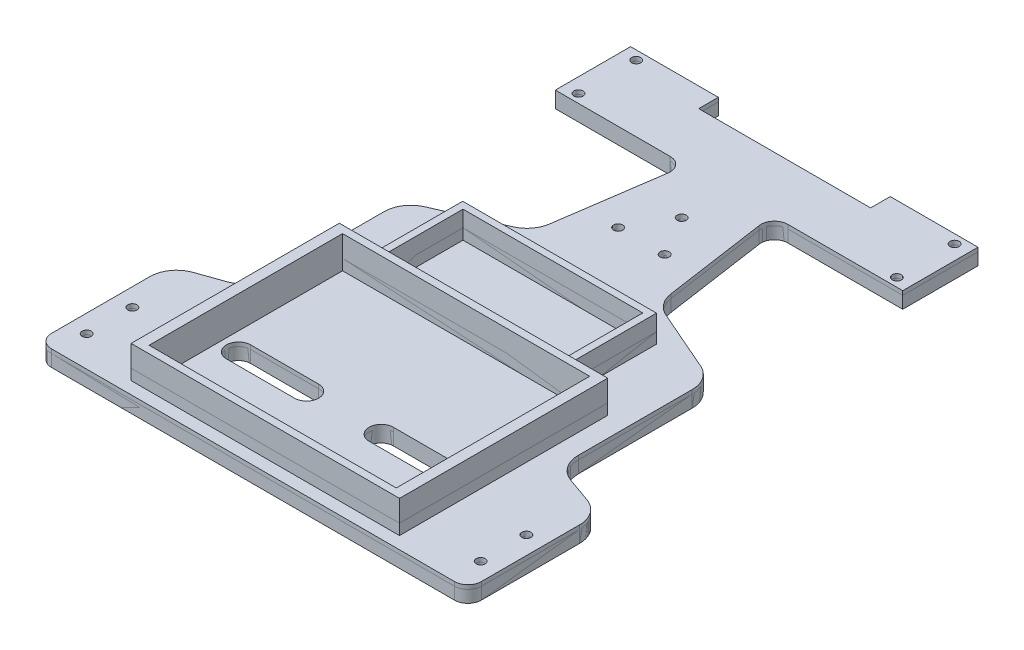
SolidWorks part; units mm, degrees
ref_plane "Front Plane" through (0, 0, 0) normal (0, 0, 1) x (1, 0, 0)
ref_plane "Top Plane" through (0, 0, 0) normal (0, 1, 0) x (1, 0, 0)
ref_plane "Right Plane" through (0, 0, 0) normal (1, 0, 0) x (0, 0, -1)
sketch "Sketch1" plane through (0, 0, 0) normal (0, 1, 0) x (1, 0, 0)
  line L1 (0, 123.1189) -> (0, -114.6431) construction
  line L5 (-80, -40.5061) -> (-80, -77.076)
  line L6 (-75, -82.076) -> (75, -82.076)
  line L28 (-51.3397, 33.1936) -> (-28.4659, 43.1635)
  line L36 (51.3397, 33.1936) -> (28.4487, 43.171)
  line L38 (-16.9584, 89.3848) -> (-22.566, 50.8891)
  line L39 (80, -40.5061) -> (80, -77.076)
  line L41 (-57.3441, 24.0265) -> (-57.3441, -18.3632)
  line L43 (57.3441, 24.0265) -> (57.3441, -18.3632)
  line L44 (-73.325, -31.075) -> (-64.0191, -27.7942)
  line L45 (64.0191, -27.7942) -> (73.325, -31.075)
  line L50 (-64.6552, 123.1189) -> (-64.6552, 95.1056)
  line L52 (64.6552, 123.1189) -> (64.6552, 95.1056)
  line L54 (16.9584, 89.3848) -> (22.553, 50.8682)
  line L55 (-64.6552, 95.1056) -> (-21.9062, 95.1056)
  line L56 (21.9062, 95.1056) -> (64.6552, 95.1056)
  line L61 (-32, 115.8044) -> (32, 115.8044)
  line L62 (32, 115.8044) -> (32, 123.1189)
  line L63 (-32, 115.8044) -> (-32, 123.1189)
  line L64 (-32, 123.1189) -> (-64.6552, 123.1189)
  line L65 (32, 123.1189) -> (64.6552, 123.1189)
  line L69 (13.8917, -48.2392) -> (39.2357, -48.2392) construction
  line L70 (13.8917, -43.7228) -> (39.2357, -43.7228)
  line L71 (13.8917, -52.7555) -> (39.2357, -52.7555)
  line L75 (-13.8917, -48.2392) -> (-39.2357, -48.2392) construction
  line L76 (-13.8917, -43.7228) -> (-39.2357, -43.7228)
  line L77 (-13.8917, -52.7555) -> (-39.2357, -52.7555)
  arc A1 (80, -77.076) -> (75, -82.076) centre (75, -77.076) cw
  arc A2 (-80, -77.076) -> (-75, -82.076) centre (-75, -77.076) ccw
  arc A5 (-28.4659, 43.1635) -> (-22.566, 50.8891) centre (-32.4616, 52.3305) ccw
  arc A6 (22.553, 50.8682) -> (28.4487, 43.171) centre (32.4444, 52.338) ccw
  arc A14 (-80, -40.5061) -> (-73.325, -31.075) centre (-70, -40.5061) cw
  arc A15 (73.325, -31.075) -> (80, -40.5061) centre (70, -40.5061) cw
  arc A16 (57.3441, -18.3632) -> (64.0191, -27.7942) centre (67.3441, -18.3632) ccw
  arc A17 (51.3397, 33.1936) -> (57.3441, 24.0265) centre (47.3441, 24.0265) cw
  arc A18 (-51.3397, 33.1936) -> (-57.3441, 24.0265) centre (-47.3441, 24.0265) ccw
  arc A19 (-57.3441, -18.3632) -> (-64.0191, -27.7942) centre (-67.3441, -18.3632) cw
  circle A20 centre (-59.25, 119.8044) radius 1.7
  circle A21 centre (-59.25, 98.3044) radius 1.7
  circle A22 centre (59.25, 98.3044) radius 1.7
  circle A23 centre (59.25, 119.8044) radius 1.7
  arc A24 (-16.9584, 89.3848) -> (-21.9062, 95.1056) centre (-21.9062, 90.1056) ccw
  arc A25 (16.9584, 89.3848) -> (21.9062, 95.1056) centre (21.9062, 90.1056) cw
  circle A26 centre (-73.325, -53.6654) radius 1.7
  circle A27 centre (-73.325, -70.6654) radius 1.7
  circle A28 centre (73.325, -70.6654) radius 1.7
  circle A29 centre (73.325, -53.6654) radius 1.7
  arc A32 (13.8917, -43.7228) -> (13.8917, -52.7555) centre (13.8917, -48.2392) ccw
  arc A33 (39.2357, -52.7555) -> (39.2357, -43.7228) centre (39.2357, -48.2392) ccw
  arc A36 (-13.8917, -43.7228) -> (-13.8917, -52.7555) centre (-13.8917, -48.2392) cw
  arc A37 (-39.2357, -52.7555) -> (-39.2357, -43.7228) centre (-39.2357, -48.2392) cw
  circle A39 centre (0, 77.4812) radius 1.7
  circle A40 centre (-8.6603, 62.4812) radius 1.7
  circle A41 centre (8.6603, 62.4812) radius 1.7
  point P7 (0, 98.3044)
  point P14 (0, -82.076)
  point P17 (0, -82.076)
  point P24 (-23.3677, 45.3856)
  point P29 (80, -45.2283)
  point P32 (80, -82.076)
  point P35 (-80, -82.076)
  point P38 (-80, -45.2283)
  point P39 (23.3677, 45.3856)
  point P42 (50, 34.4201)
  point P44 (-80, -33.4284)
  point P47 (80, -33.4284)
  point P51 (-50, 34.4201)
  point P52 (57.3441, -25.4409)
  point P55 (57.3441, 30.5765)
  point P58 (-57.3441, 30.5765)
  point P61 (-57.3441, -25.4409)
  point P66 (0, 95.1492)
  point P67 (0, 119.8044)
  point P69 (0, 125.9925)
  point P73 (0, 115.8044)
  point P76 (-16.1251, 95.1056)
  point P79 (16.1251, 95.1056)
  point P95 (26.5637, -48.2392)
  point P101 (0, 67.4812)
  point P109 (-26.5637, -48.2392)
  dimension "D7" = 10
  dimension "D8" = 64
  dimension "D10" = 118.5
  dimension "D11" = 7.3144
  dimension "D4" = 5
  dimension "D9" = 21.5
  dimension "D12" = 28.0133
  dimension "D13" = 32.6552
  dimension "D1" = 160
  dimension "D2" = 59.25
  dimension "D3" = 0
  dimension "D5" = 36.8477
  dimension "D6" = 116.4961
extrude "Boss-Extrude2" add sketch "Sketch1" along normal blind 6
sketch "Sketch2" plane through (0, 6, 0) normal (0, 1, 0) x (1, 0, 0)
  line L1 (46, -2.7522) -> (-46, -2.7522)
  line L2 (46, -2.7522) -> (46, -74.7522)
  line L3 (46, -74.7522) -> (-46, -74.7522)
  line L4 (-46, -2.7522) -> (-46, -74.7522)
  line L5 (46, -2.7522) -> (-46, -74.7522) construction
  line L6 (46, -74.7522) -> (-46, -2.7522) construction
  line L7 (-49.9483, -77.5045) -> (49.9483, -77.5045)
  line L8 (-49.9483, -77.5045) -> (-49.9483, 0)
  line L9 (-49.9483, 0) -> (49.9483, 0)
  line L10 (49.9483, -77.5045) -> (49.9483, 0)
  line L11 (-49.9483, -77.5045) -> (49.9483, 0) construction
  line L12 (-49.9483, 0) -> (49.9483, -77.5045) construction
  point P0 (0, -38.7522)
  point P5 (0, -38.7522)
  dimension "D1" = 92
  dimension "D2" = 72
  dimension "D3" = 3.9483
sketch "Sketch4" plane through (0, 6, 0) normal (0, 1, 0) x (1, 0, 0)
extrude "Boss-Extrude3" add sketch "Sketch2" along normal blind 12
sketch "Sketch8" plane through (0, 6, 0) normal (0, 1, 0) x (1, 0, 0)
  line L1 (-36.0682, 0.0375) -> (36.0682, 0.0375)
  line L2 (-36.0682, 0.0375) -> (-36.0682, 32.0375)
  line L3 (-36.0682, 32.0375) -> (36.0682, 32.0375)
  line L4 (36.0682, 0.0375) -> (36.0682, 32.0375)
  line L5 (-36.0682, 0.0375) -> (36.0682, 32.0375) construction
  line L6 (-36.0682, 32.0375) -> (36.0682, 0.0375) construction
  line L9 (33.4608, 29.5424) -> (-33.4608, 29.5424)
  line L10 (33.4608, 29.5424) -> (33.4608, 0.0375)
  line L11 (33.4608, 0.0375) -> (-33.4608, 0.0375)
  line L12 (-33.4608, 29.5424) -> (-33.4608, 0.0375)
  point P0 (0, 16.0375)
  point P10 (0, 29.5424)
  dimension "D1" = 72.1363
  dimension "D2" = 32
  dimension "D3" = 66.9216
extrude "Boss-Extrude7" add sketch "Sketch8" along normal blind 10 contours L12 L9 L10 L1 L4 L3 L2 region at (-35.279, 6, -16.0375)
extrude "Boss-Extrude9" add sketch "Sketch2<3>" along normal blind 4 and the other way blind 2 separate body
sketch "Sketch2<3>" plane through (0, 6, 0) normal (0, 1, 0) x (1, 0, 0) same geometry as "Sketch2"
extrude "Boss-Extrude10" add sketch "Sketch1<3>" along normal blind 0.001 and the other way blind 0.01
sketch "Sketch1<3>" plane through (0, 0, 0) normal (0, 1, 0) x (1, 0, 0) same geometry as "Sketch1"
extrude "Boss-Extrude11" add sketch "Sketch8<9>" along normal blind 4 and the other way blind 2 contours L12 L9 L10 L1 L4 L3 L2 region at (-35.279, 6, -16.0375)
sketch "Sketch8<9>" plane through (0, 6, 0) normal (0, 1, 0) x (1, 0, 0) same geometry as "Sketch8"
extrude "Boss-Extrude13" add sketch "Sketch1<5>" along normal blind 4.5
sketch "Sketch1<5>" plane through (0, 0, 0) normal (0, 1, 0) x (1, 0, 0) same geometry as "Sketch1"
